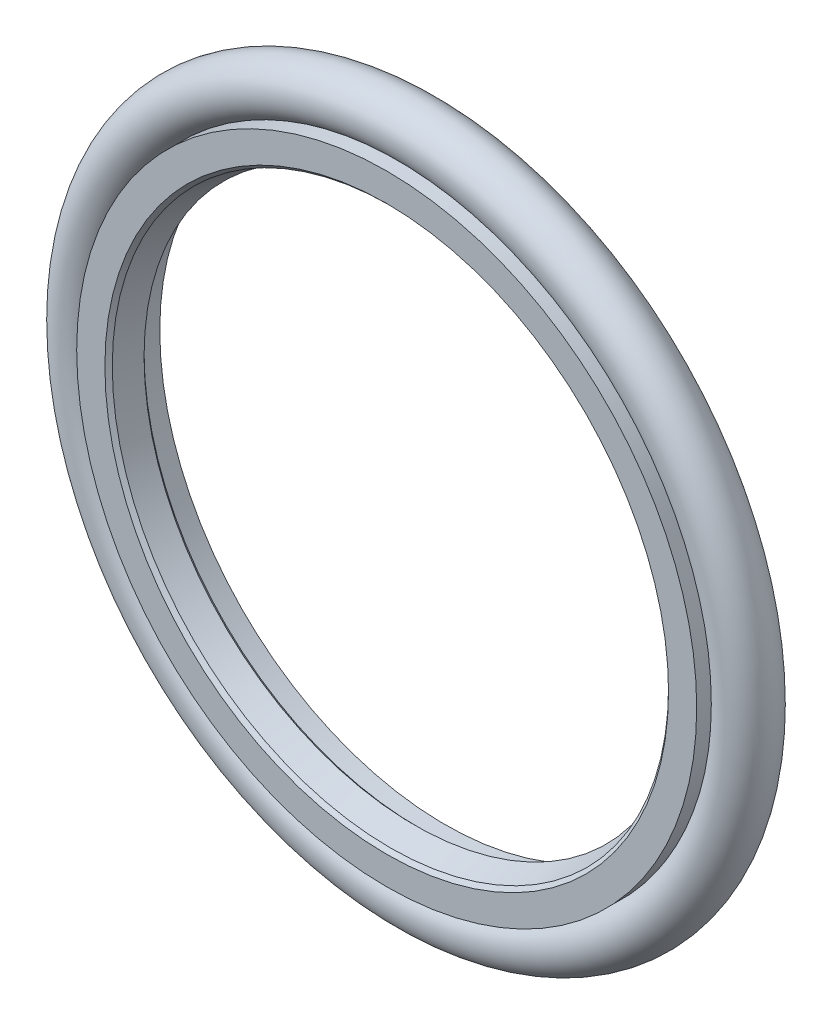
SolidWorks part; units mm, degrees
material "PTFE+NBR"
ref_plane "Front Plane" through (0, 0, 0) normal (0, 0, 1) x (1, 0, 0)
ref_plane "Top Plane" through (0, 0, 0) normal (0, 1, 0) x (1, 0, 0)
ref_plane "Right Plane" through (0, 0, 0) normal (1, 0, 0) x (0, 0, -1)
sketch "Sketch1" plane through (0, 0, 0) normal (1, 0, 0) x (0, 0, -1)
  line L0 (0, 19.25) -> (0, 20.9)
  line L1 (-3.95, 20.9) -> (0, 20.9)
  line L2 (-3.95, 20.9) -> (-3.95, 19)
  line L3 (-1.975, 20.9) -> (-1.975, 52.9493) construction
  line L4 (-3.95, 19) -> (-3.7, 18.7514)
  line L5 (-1.81, 18.5) -> (-1.81, 19)
  line L6 (0, 0) -> (-16.4728, 0) construction
  line L7 (0, 19.25) -> (-1.56, 19.25)
  line L8 (-1.81, 18.5) -> (-2.06, 18.25)
  line L9 (-3.95, 20.9) -> (0, 20.9) construction
  line L11 (-2.06, 18.25) -> (-3.7, 18.7514)
  arc A0 (-1.81, 19) -> (-1.56, 19.25) centre (-1.56, 19) cw
  dimension "D2" = 1.65
  dimension "D4" = 2.65
  dimension "D10" = 0.25
  dimension "D1" = 3.95
  dimension "D3" = 36.5
  dimension "D5" = 1.81
  dimension "D6" = 1.9
  dimension "D7" = 17
  dimension "D8" = 0.25
  dimension "D9" = 0.25
  dimension "D11" = 45
revolve "Revolve1" add sketch "Sketch1" angle 360 about L6
sketch "Sketch4" plane through (0, 0, 0) normal (1, 0, 0) x (0, 0, -1)
  line L0 (0, 0) -> (-3.95, 0) construction
  line L2 (-1.975, 0) -> (-1.975, 52.8756) construction
  line L3 (-3.95, 20.9) -> (-3.95, -20.9) construction
  circle A0 centre (-1.975, 22.405) radius 1.765
  dimension "D1" = 41.28
  dimension "D2" = 3.53
revolve "Revolve2" add sketch "Sketch4" angle 360 about L0
ref_axis "Axis1" through (0, 0, 0) along (0, 0, 1)
